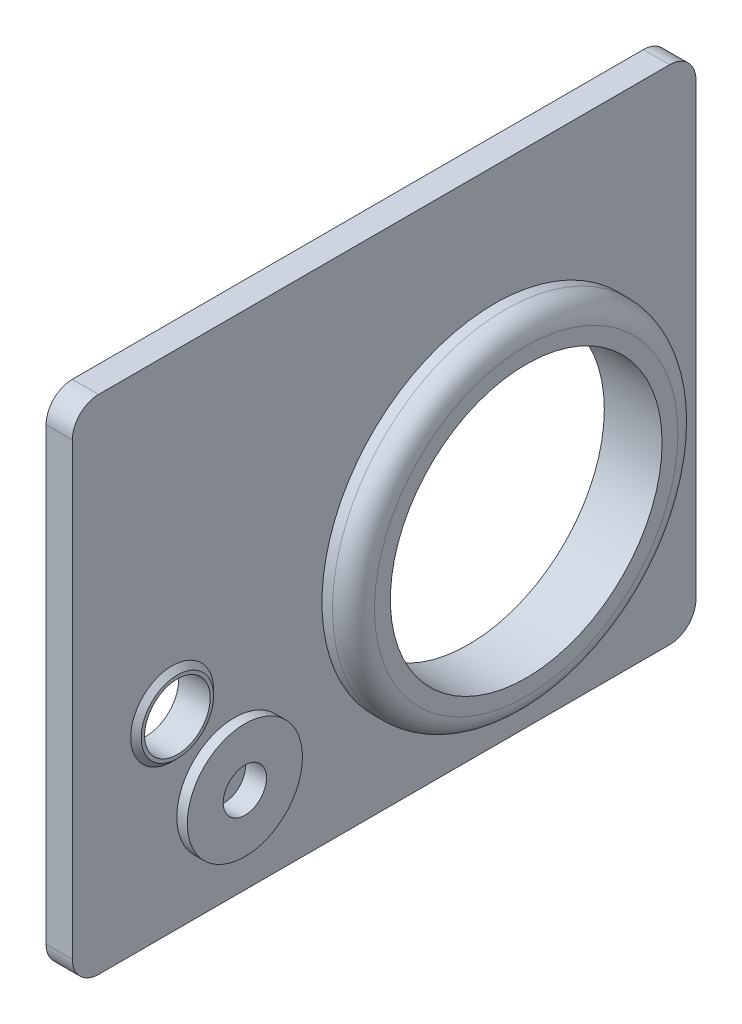
SolidWorks part; units mm, degrees
ref_plane "Front" through (0, 0, 0) normal (0, 0, 1) x (1, 0, 0)
ref_plane "Top" through (0, 0, 0) normal (0, 1, 0) x (1, 0, 0)
ref_plane "Right" through (0, 0, 0) normal (1, 0, 0) x (0, 0, -1)
sketch "Sketch1" plane through (0, 0, 0) normal (1, 0, 0) x (0, 0, -1)
  line L0 (-54.3692, 47.8186) -> (54.3692, 47.8186) construction
  line L1 (-59.3692, -47.8186) -> (59.3692, -47.8186)
  line L2 (-59.3692, -47.8186) -> (-59.3692, 47.8186)
  line L3 (-59.3692, 47.8186) -> (59.3692, 47.8186)
  line L4 (59.3692, -47.8186) -> (59.3692, 47.8186)
  line L5 (-59.3692, -47.8186) -> (59.3692, 47.8186) construction
  line L6 (-59.3692, 47.8186) -> (59.3692, -47.8186) construction
  circle A0 centre (21.0527, -7.7825) radius 32.8876
  circle A1 centre (-28.5137, -29.3663) radius 10.9631
  circle A2 centre (-28.5137, -29.3663) radius 4.1306
  circle A3 centre (-40.3633, -11.8261) radius 6.2436
  circle A4 centre (21.0527, -7.7825) radius 25.869
  circle A5 centre (-40.3633, -11.8261) radius 7.8948
  point P0 (0, 0)
extrude "Boss-Extrude1" add sketch "Sketch1" along normal blind 5 contours L1 L4 L3 L2 A5 A1 A0 region at (0, 0, 57.8445)
extrude "Boss-Extrude2" add sketch "Sketch1<3>" along normal blind 11 contours A0 A4 region at (0, -7.7825, 10.9047)
sketch "Sketch1<3>" plane through (0, 0, 0) normal (1, 0, 0) x (0, 0, -1) same geometry as "Sketch1"
fillet "Fillet1" radius 4 1 edges at (11, -7.7825, -53.9403)
extrude "Boss-Extrude3" add sketch "Sketch1<4>" along normal blind 7 contours A1 A2 region at (0, -29.3663, 39.1667)
sketch "Sketch1<4>" plane through (0, 0, 0) normal (1, 0, 0) x (0, 0, -1) same geometry as "Sketch1"
extrude "Boss-Extrude4" add sketch "Sketch1<5>" along normal blind 6 contours A5 A3 region at (0, -11.8261, 48.0348)
sketch "Sketch1<5>" plane through (0, 0, 0) normal (1, 0, 0) x (0, 0, -1) same geometry as "Sketch1"
chamfer "Chamfer1" distance 1 angle 45 1 edges at (6, -11.8261, 32.4685)
fillet "Fillet2" radius 5 4 edges at (2.5, 47.8186, -59.3692) (2.5, -47.8186, -59.3692) (2.5, -47.8186, 59.3692) (2.5, 47.8186, 59.3692)
extrude "Boss-Extrude5" add sketch "Sketch1<6>" along normal blind 3 contours A2
sketch "Sketch1<6>" plane through (0, 0, 0) normal (1, 0, 0) x (0, 0, -1) same geometry as "Sketch1"
